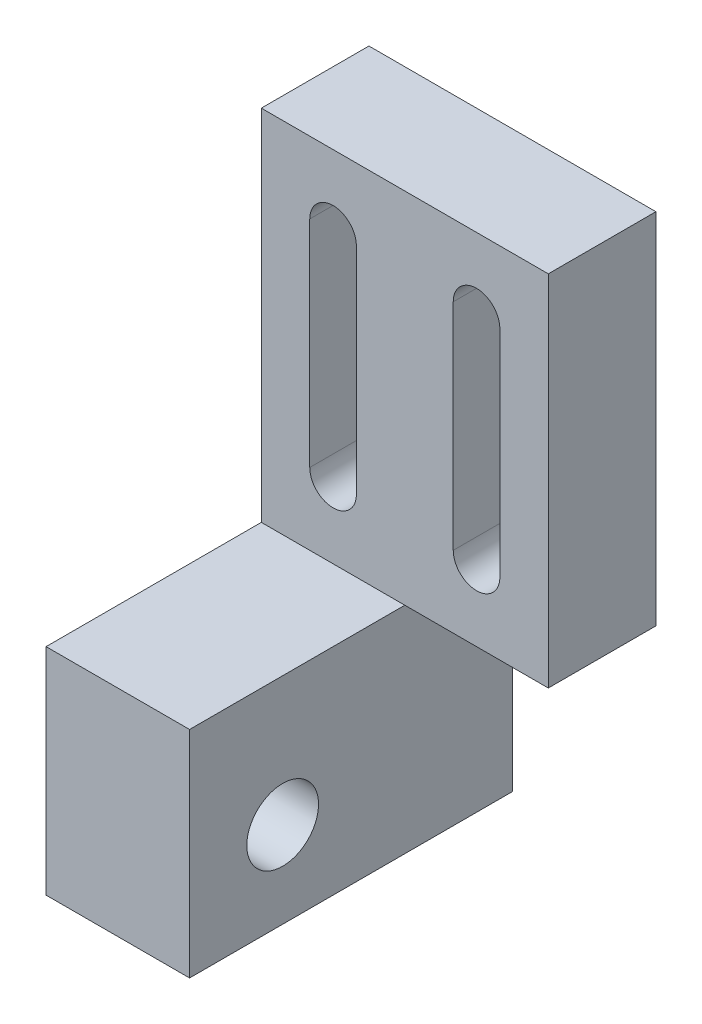
SolidWorks part; units mm, degrees
material "ABS"
ref_plane "前视基准面" through (0, 0, 0) normal (0, 0, 1) x (1, 0, 0)
ref_plane "上视基准面" through (0, 0, 0) normal (0, 1, 0) x (1, 0, 0)
ref_plane "右视基准面" through (0, 0, 0) normal (1, 0, 0) x (0, 0, -1)
other "Configuration Table"
sketch "草图1" plane through (0, 0, 0) normal (0, 0, 1) x (1, 0, 0)
  line L0 (-84.6, 0.27) -> (-68.7, 0.27) construction
  line L1 (-84.6, 6.27) -> (-80.6, 6.27)
  line L2 (-84.6, 6.27) -> (-84.6, 0.27)
  line L3 (-84.6, 0.27) -> (-80.6, 0.27)
  line L4 (-80.6, 6.27) -> (-80.6, 0.27)
  dimension "D1" = 6
  dimension "D2" = 4
extrude "凸台-拉伸1" add sketch "草图1" along normal blind 9
sketch "草图5" plane through (0, 0, 0) normal (0, 0, 1) x (1, 0, 0)
  line L1 (-84.6, 6.27) -> (-76.6, 6.27)
  line L2 (-84.6, 6.27) -> (-84.6, 16.27)
  line L3 (-84.6, 16.27) -> (-76.6, 16.27)
  line L4 (-76.6, 6.27) -> (-76.6, 16.27)
  dimension "D1" = 10
  dimension "D2" = 8
extrude "凸台-拉伸3" add sketch "草图5" along normal blind 3
sketch "草图7" plane through (-84.6, 0, 0) normal (-1, 0, 0) x (0, 0, 1)
  line L6 (0, 16.27) -> (0, 0.27)
  line L7 (0, 0.27) -> (9, 0.27)
  line L8 (9, 0.27) -> (9, 6.27)
  line L9 (9, 6.27) -> (3, 6.27)
  line L10 (3, 6.27) -> (3, 16.27)
  line L11 (3, 16.27) -> (0, 16.27)
  line L12 (0, 16.27) -> (0, 0.27)
  line L13 (0, 0.27) -> (9, 0.27)
  line L14 (9, 0.27) -> (9, 6.27)
  line L15 (9, 6.27) -> (3, 6.27)
  line L16 (3, 6.27) -> (3, 16.27)
  line L17 (3, 16.27) -> (0, 16.27)
  arc A0 (5.755, 3.4299) -> (7.055, 3.4299) centre (6.405, 2.67) ccw construction
  arc A1 (5.755, 3.4299) -> (7.055, 3.4299) centre (6.405, 2.67) ccw
  circle A2 centre (6.405, 2.67) radius 1
  dimension "D2" = 2
  dimension "D1" = 0
extrude "切除-拉伸4" cut sketch "草图7" against normal through all contours A1 A2 region at (-84.6, 2.67, 6.405)
sketch "草图8" plane through (0, 0, 3) normal (0, 0, 1) x (1, 0, 0)
  line L0 (-82.6, 8.27) -> (-82.6, 14.27) construction
  line L1 (-83.25, 8.27) -> (-83.25, 14.27)
  line L2 (-81.95, 8.27) -> (-81.95, 14.27)
  line L3 (-78.6, 14.27) -> (-78.6, 8.27) construction
  line L4 (-77.95, 14.27) -> (-77.95, 8.27)
  line L5 (-79.25, 14.27) -> (-79.25, 8.27)
  line L6 (-80.6, 20.5485) -> (-80.6, 3.956) construction
  line L10 (-76.6, 6.27) -> (-76.6, 16.27) construction
  line L11 (-84.6, 16.27) -> (-84.6, 6.27) construction
  line L12 (-86.6279, 11.27) -> (-75.4887, 11.27) construction
  line L14 (-76.6, 16.27) -> (-84.6, 16.27) construction
  line L15 (-80.6, 6.27) -> (-76.6, 6.27) construction
  arc A0 (-83.25, 8.27) -> (-81.95, 8.27) centre (-82.6, 8.27) ccw
  arc A1 (-81.95, 14.27) -> (-83.25, 14.27) centre (-82.6, 14.27) ccw
  arc A2 (-77.95, 14.27) -> (-79.25, 14.27) centre (-78.6, 14.27) ccw
  arc A3 (-79.25, 8.27) -> (-77.95, 8.27) centre (-78.6, 8.27) ccw
  point P2 (-82.6, 11.27)
  point P8 (-78.6, 11.27)
  dimension "D1" = 1.3
  dimension "D2" = 2
  dimension "D3" = 4
extrude "切除-拉伸5" cut sketch "草图8" against normal through all
